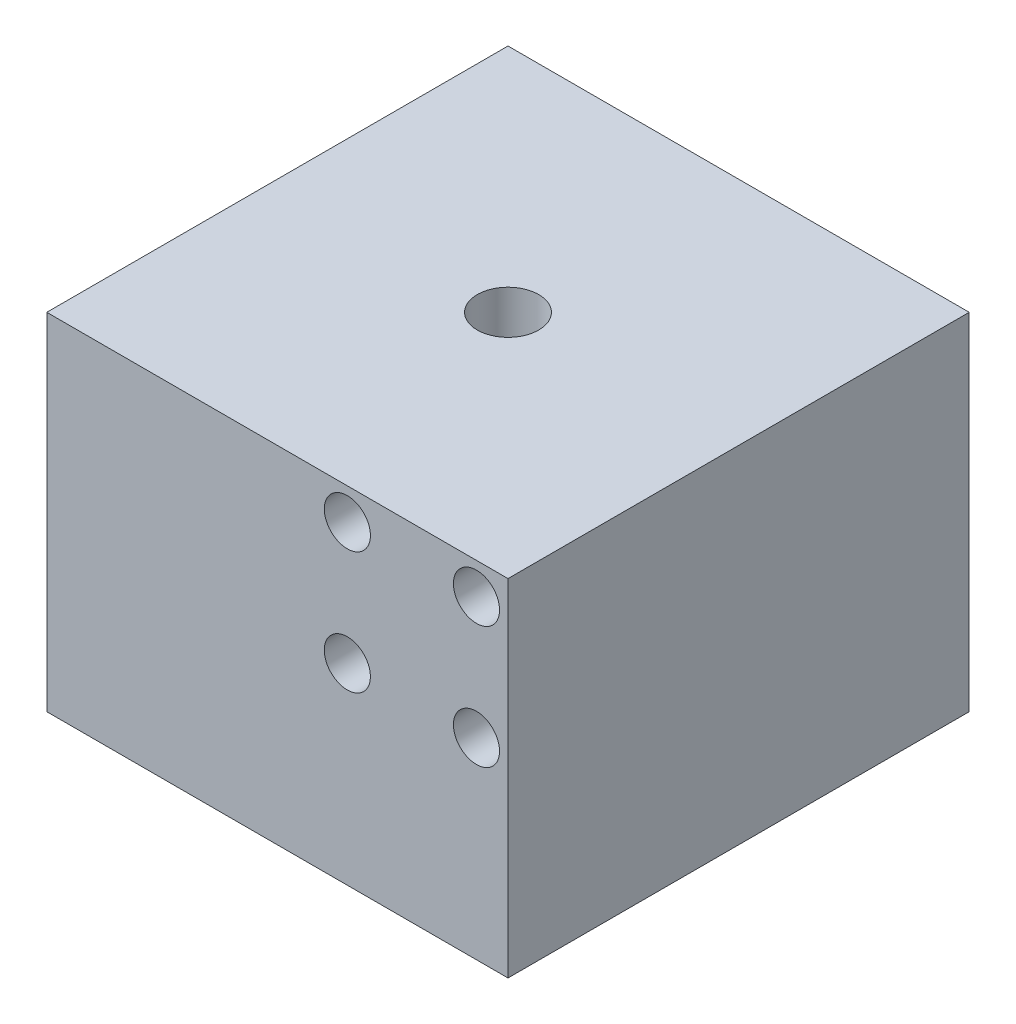
SolidWorks part; units mm, degrees
ref_plane "정면" through (0, 0, 0) normal (0, 0, 1) x (1, 0, 0)
ref_plane "윗면" through (0, 0, 0) normal (0, 1, 0) x (1, 0, 0)
ref_plane "우측면" through (0, 0, 0) normal (1, 0, 0) x (0, 0, -1)
sketch "스케치1" plane through (0, 0, 0) normal (0, 0, 1) x (1, 0, 0)
  line L1 (-30, 22.5) -> (30, 22.5)
  line L2 (-30, 22.5) -> (-30, -22.5)
  line L3 (-30, -22.5) -> (30, -22.5)
  line L4 (30, 22.5) -> (30, -22.5)
  line L5 (-30, 22.5) -> (30, -22.5) construction
  line L6 (-30, -22.5) -> (30, 22.5) construction
  point P4 (0, 0)
  point P5 (0, 0)
  dimension "D1" = 60
  dimension "D2" = 45
extrude "보스-돌출1" add sketch "스케치1" along normal blind 60
ref_plane "평면1" through (0, 0, 30) normal (0, 0, -1) x (-1, 0, 0)
sketch "스케치2" plane through (0, 0, 30) normal (0, 0, -1) x (-1, 0, 0)
  line L0 (0, 17.5) -> (0, -22.5)
  line L1 (0, -22.5) -> (-27, -22.5)
  line L2 (-27, -22.5) -> (0, 17.5)
  line L3 (30, -22.5) -> (-30, -22.5) construction
  point P6 (0, 0)
  dimension "D1" = 40
  dimension "D2" = 27
revolve "컷-회전1" cut sketch "스케치2" angle 360 about L0
sketch "스케치3" plane through (0, 22.5, 0) normal (0, 1, 0) x (1, 0, 0)
  line L0 (24.75, -30) -> (-24.75, -30) construction
  circle A0 centre (0, -30) radius 4
  point P4 (0, 0)
  dimension "D1" = 8
extrude "컷-돌출1" cut sketch "스케치3" against normal through all both contours A0
sketch "스케치4" plane through (0, 0, 0) normal (0, 0, -1) x (-1, 0, 0)
  line L0 (-30, 22.5) -> (30, 22.5) construction
  line L1 (-30, 22.5) -> (-5, 22.5) construction
  line L2 (-30, 22.5) -> (-30, -1.6) construction
  line L3 (-30, -1.6) -> (-5, -1.6) construction
  line L4 (-5, 22.5) -> (-5, -1.6) construction
  line L5 (-30, 22.5) -> (-5, -1.6) construction
  line L6 (-30, -1.6) -> (-5, 22.5) construction
  line L7 (-30, -22.5) -> (-30, 22.5) construction
  line L8 (-17.5, -1.6) -> (-17.5, 10.45) construction
  line L9 (-17.5, 10.45) -> (-30, 10.45) construction
  circle A0 centre (-25.9, 18.4) radius 3
  circle A1 centre (-25.9, 2.5) radius 3
  circle A2 centre (-9.1, 18.4) radius 3
  circle A3 centre (-9.1, 2.5) radius 3
  point P4 (-17.5, 10.45)
  dimension "D3" = 6
  dimension "D4" = 4.1
  dimension "D5" = 4.1
  dimension "D1" = 25
  dimension "D2" = 24.1
extrude "컷-돌출2" cut sketch "스케치4" against normal through all both
ref_axis "기준축1" through (27, -22.5, 30) along (-0.5595, 0.8288, 0)
sketch "스케치5" plane through (0, 0, 30) normal (0, 0, -1) x (-1, 0, 0)
  line L0 (0, 17.5) -> (27, -22.5) construction
  line L1 (-27, -22.5) -> (27, -22.5) construction
  line L2 (15.3706, 3.5764) -> (27.9587, -15.0727)
  line L3 (27.9587, -15.0727) -> (30, -13.6948)
  line L5 (15.3706, 3.5764) -> (11.1745, 9.7928)
  line L6 (11.1745, 9.7928) -> (30, 22.5)
  line L7 (-30, 22.5) -> (30, 22.5) construction
  line L8 (30, 22.5) -> (30, -22.5) construction
  line L9 (30, 22.5) -> (30, -13.6948)
  point P4 (0, -22.5)
  point P10 (30, 22.5)
  point P12 (0, 0)
  dimension "D1" = 9.9
  dimension "D3" = 30
extrude "컷-돌출8" cut sketch "스케치5" against normal mid plane 14.4 contours L6 L9 L3 L2 L5
sketch "스케치6" plane through (-12.2179, 8.2471, 0) normal (-0.8288, 0.5595, 0) x (0, 0, 1)
  line L0 (37.2, -28.1351) -> (37.2, 1.8649) construction
  line L1 (22.8, 1.8649) -> (37.2, 1.8649)
  line L2 (22.8, 1.8649) -> (22.8, -4.8351)
  line L3 (22.8, -4.8351) -> (37.2, -4.8351)
  line L4 (37.2, 1.8649) -> (37.2, -4.8351)
  line L5 (22.8, 1.8649) -> (37.2, -4.8351) construction
  line L6 (22.8, -4.8351) -> (37.2, 1.8649) construction
  point P4 (30, -1.4851)
  dimension "D1" = 6.7
extrude "컷-돌출9" cut sketch "스케치6" against normal up to next
